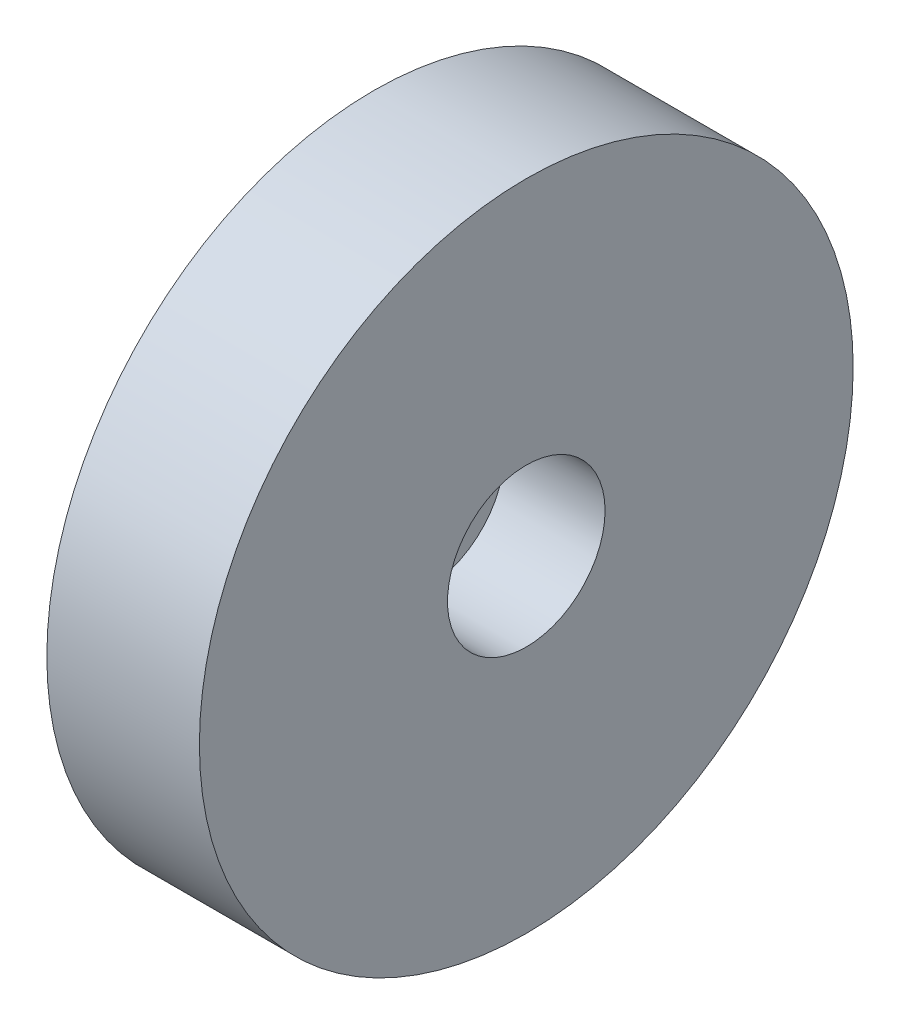
SolidWorks part; units mm, degrees
ref_plane "Plane1" through (0, 0, 0) normal (0, 0, 1) x (1, 0, 0)
ref_plane "Plane2" through (0, 0, 0) normal (0, 1, 0) x (1, 0, 0)
ref_plane "Plane3" through (0, 0, 0) normal (1, 0, 0) x (0, 0, -1)
sketch "HoldingSke" plane through (0, 0, 0) normal (0, 1, 0) x (1, 0, 0)
  line L0 (0, 0) -> (0.9272, -0.3746)
  line L1 (-15, 0) -> (100, 0) construction
  line L2 (0, 0) -> (-2.1039, 2.3779)
  line L3 (0, 0) -> (-11.863, 4.5341)
  line L4 (0, 0) -> (8.0072, 3.2351)
  line L5 (0, 0) -> (-46.8476, -17.4728)
  line L6 (0, 0) -> (-3.7718, -2.5448)
  line L7 (-2.1039, 2.3779) -> (8.6586, 51.2059)
  line L8 (-76.2, 54.61) -> (-75.5, 54.61)
  line L9 (-71.009, 38.7566) -> (-53.1078, 45.2721)
  line L10 (-76.2, 71.12) -> (104.1128, 71.12)
  line L11 (0, 0) -> (-4.55, 0)
  line L12 (-76.2, 101.6) -> (-76.162, 101.6)
  line L13 (24.9733, 27.94) -> (52.9518, 28.4284)
  line L14 (24.9733, 27.94) -> (24.9743, 27.94)
  line L15 (24.9733, 27.94) -> (100.4006, 29.5858)
  line L16 (-63.627, -1) -> (-12.827, -1)
  circle A0 centre (0, 0) radius 2
  circle A1 centre (0, 0) radius 9.749
  circle A2 centre (0, 0) radius 37.5
  circle A3 centre (0, 0) radius 2
  dimension "Num_teeth" = 22
  dimension "Pitch_radius" = 180.3128
  dimension "Width" = 4.55
  dimension "Thickness" = 4.55
sketch "BasProSke" plane through (0, 0, 0) normal (0, 1, 0) x (1, 0, 0)
  line L0 (-10, 0) -> (60, 0) construction
  line L1 (0, 0) -> (0, 12)
  line L2 (0, 0) -> (4.55, 0)
  line L3 (4.55, 0) -> (4.55, 12)
  line L4 (4.55, 12) -> (0, 12)
  dimension "Thickness" = 4.55
  dimension "Diameter" = 24
revolve "Base-Revolve" add sketch "BasProSke" angle 360 about L0
sketch "TooCutSke" plane through (0, 0, 0) normal (1, 0, 0) x (0, 0, -1)
  line L1 (0, 0) -> (0, 107) construction
  line L2 (0, 0) -> (-2.273, 10.7626) construction
  line L3 (0, 0) -> (-3.1242, 21.7296) construction
  line L4 (-2.273, 10.7626) -> (-1.5621, 10.8648) construction
  arc A0 (1.7556, 9.5896) -> (-1.7556, 9.5896) centre (0, 0) ccw
  arc A1 (3.0039, 11.6442) -> (-3.0039, 11.6442) centre (0, 0) ccw
  circle A2 centre (0, 0) radius 11 construction
  circle A3 centre (0, 0) radius 10.3366 construction
  arc A4 (-1.7556, 9.5896) -> (-3.0039, 11.6442) centre (-5.997, 8.4191) ccw
  arc A5 (3.0039, 11.6442) -> (1.7556, 9.5896) centre (5.997, 8.4191) ccw
extrude "ToothCut" cut sketch "TooCutSke" along normal through all
fillet "Breaks" [suppressed] radius 0.02 tangent propagation no
fillet "RootFillets" [suppressed] radius 0.251
pattern_circular "TeethCuts" count 22 every 16.364 about axis through (-10, 0, 0) along (1, 0, 0) of "ToothCut", "RootFillets", "Breaks"
sketch "HubNeaOneSke" plane through (0, 0, 0) normal (-1, 0, 0) x (0, 0, 1)
  circle A0 centre (0, 0) radius 9.749
  dimension "Diameter" = 19.498
extrude "HubNearOne" [suppressed] add sketch "HubNeaOneSke" along normal blind 45.4501
sketch "HubNeaBotSke" plane through (0, 0, 0) normal (-1, 0, 0) x (0, 0, 1)
  circle A0 centre (0, 0) radius 9.749
  dimension "Diameter" = 19.498
extrude "HubNearBoth" [suppressed] add sketch "HubNeaBotSke" along normal blind 22.725
ref_plane "FarPln" through (4.55, 0, 0) normal (1, 0, 0) x (0, 0, -1)
sketch "HubFarSke" plane through (4.55, 0, 0) normal (1, 0, 0) x (0, 0, -1)
  circle A0 centre (0, 0) radius 9.749
  dimension "Diameter" = 19.498
extrude "HubFar" [suppressed] add sketch "HubFarSke" along normal blind 22.725
sketch "BorSke" plane through (0, 0, 0) normal (1, 0, 0) x (0, 0, -1)
  circle A0 centre (0, 0) radius 1.35
  dimension "Diameter" = 2.7
extrude "Bore" cut sketch "BorSke" along normal mid plane 100.0001
sketch "KeySke" plane through (0, 0, 0) normal (1, 0, 0) x (0, 0, -1)
  line L0 (-0.8, 0) -> (-0.8, 2.7)
  line L1 (-0.8, 2.7) -> (0.8, 2.7)
  line L2 (0.8, 2.7) -> (0.8, 0)
  line L3 (0, 0) -> (0, 34) construction
  line L4 (-0.8, 0) -> (0.8, 0)
  dimension "Width" = 1.6
extrude "Keyway" [suppressed] cut sketch "KeySke" along normal mid plane 100.0001
pattern_circular "Keyway2" [suppressed] count 2 every 90 about axis through (-10, 0, 0) along (1, 0, 0) reverse direction yes
sketch "Sketch1" plane through (0, 0, 0) normal (-1, 0, 0) x (0, 0, 1)
  circle A0 centre (0, 0) radius 4
  circle A1 centre (0, 0) radius 6
  circle A2 centre (0, 0) radius 1.35 construction
  circle A3 centre (0, 0) radius 1.35
  dimension "D1" = 8
  dimension "D2" = 12
extrude "Boss-Extrude1" add sketch "Sketch1" along normal blind 4 contours A0 region at (0, 0, -3.8869)
extrude "Boss-Extrude2" add sketch "Sketch1<4>" along normal blind 1 contours A1 A0 region at (0, 0, -5.8303)
sketch "Sketch1<4>" plane through (0, 0, 0) normal (-1, 0, 0) x (0, 0, 1) same geometry as "Sketch1"
sketch "Sketch2" plane through (4.55, 0, 0) normal (1, 0, 0) x (0, 0, -1)
  circle A0 centre (0, 0) radius 2.35
  circle A1 centre (0, 0) radius 4.35
  dimension "D1" = 4.7
  dimension "D2" = 2
extrude "Boss-Extrude3" [suppressed] add sketch "Sketch2" along normal blind 2.5
fillet "Fillet1" [suppressed] radius 0.5
extrude "Cut-Extrude1" cut sketch "Sketch2<2>" against normal blind 3 contours A0 region at (4.55, 0, 0)
sketch "Sketch2<2>" plane through (4.55, 0, 0) normal (1, 0, 0) x (0, 0, -1) same geometry as "Sketch2"
equation "' \"Module@HoldingSke\" = 6.35"
equation "' \"Num_teeth@HoldingSke\" = 12"
equation "' \"Ap@HoldingSke\" =  20"
equation "' \"Ap@HoldingSke\" = 20"
equation "' \"Width@HoldingSke\" = 0.5 * 25.4"
equation "' \"Hub_dia@HoldingSke\"= 1 * 25.4"
equation "' \"Hub_dia@HoldingSke\" = 1 * 25.4"
equation "' \"Overall_len@HoldingSke\" = 1.0 * 25.4"
equation "' \"Bore@HoldingSke\" = 0.75 * 25.4"
equation "' \"T_dim@HoldingSke\" = 0.1 * 25.4"
equation "' \"Width@KeySke\" = 0.25 * 25.4"
equation "' \"Show_teeth@HoldingSke\" = 13"
equation "' \"Backlash@HoldingSke\" = 0.009 * 25.4"
equation "' \"Addendum_fac@HoldingSke\" = 1.0"
equation "' \"Dedendum_fac@HoldingSke\" = 1.25"
equation "' \"Dedendum_add@HoldingSke\" = 0.00005 * 25.4"
equation "' \"Clearance_fac@HoldingSke\" = 0.25"
equation "\"Pitch@HoldingSke\" = 1 / \"Module@HoldingSke\""
equation "\"Overcut_dia@TooCutSke\" = (\"Num_teeth@HoldingSke\" + 2 * \"Addendum_fac@HoldingSke\") / \"Pitch@HoldingSke\" + 0.002 * 25.4"
equation "\"Pitch_dia@TooCutSke\" = \"Num_teeth@HoldingSke\" / \"Pitch@HoldingSke\""
equation "\"Base_dia@TooCutSke\" = \"Num_teeth@HoldingSke\" / \"Pitch@HoldingSke\" * cos((\"Ap@HoldingSke\"  * 3.14159265 / 180))"
equation "\"Root_dia@TooCutSke\" = (\"Num_teeth@HoldingSke\" + 2) / \"Pitch@HoldingSke\" - 2 * (\"Addendum_fac@HoldingSke\" + \"Dedendum_fac@HoldingSke\") / \"Pitch@HoldingSke\" - \"Dedendum_add@HoldingSke\" * 2"
equation "\"Half_ang@TooCutSke\" = 180 / \"Num_teeth@HoldingSke\""
equation "\"Half_CT@TooCutSke\" = \"Num_teeth@HoldingSke\" / \"Pitch@HoldingSke\" * sin((3.14159265 / 2 / \"Num_teeth@HoldingSke\")) / 2 - 7 * \"Backlash@HoldingSke\" / 4"
equation "\"Flank_rad@TooCutSke\" = \"Num_teeth@HoldingSke\" / \"Pitch@HoldingSke\" / 5"
equation "\"Radius@RootFillets\" = \"Clearance_fac@HoldingSke\" / \"Pitch@HoldingSke\" + \"Dedendum_add@HoldingSke\""
equation "\"Break_rad@Breaks\" = 0.02 / \"Pitch@HoldingSke\""
equation "\"Thickness@HoldingSke\" = \"Width@HoldingSke\""
equation "\"OAL@HoldingSke\" = \"Thickness@HoldingSke\""
equation "\"MHD@HoldingSke\" = (\"Num_teeth@HoldingSke\" + 2) / \"Pitch@HoldingSke\" - 2 * (\"Addendum_fac@HoldingSke\" + \"Dedendum_fac@HoldingSke\")  / \"Pitch@HoldingSke\" - \"Dedendum_add@HoldingSke\" * 2"
equation "\"MBD@HoldingSke\" = (\"Num_teeth@HoldingSke\" + 2) / \"Pitch@HoldingSke\" - 2 * (\"Addendum_fac@HoldingSke\" + \"Dedendum_fac@HoldingSke\")  / \"Pitch@HoldingSke\" - \"Dedendum_add@HoldingSke\" * 2 - 0.002 * 25.4"
equation "\"MHD@HoldingSke\" = ((sgn( \"MHD@HoldingSke\" - \"Hub_dia@HoldingSke\" )-1)*( \"MHD@HoldingSke\" - \"Hub_dia@HoldingSke\" ))/-2+ \"Hub_dia@HoldingSke\""
equation "\"MBD@HoldingSke\" = ((sgn( \"MBD@HoldingSke\" - \"Bore@HoldingSke\" )-1)*( \"MBD@HoldingSke\" - \"Bore@HoldingSke\" ))/-2+ \"Bore@HoldingSke\""
equation "\"OAL@HoldingSke\" = ((sgn( \"OAL@HoldingSke\" - \"Overall_len@HoldingSke\" )+1)*( \"OAL@HoldingSke\" - \"Overall_len@HoldingSke\" ))/2 + \"Overall_len@HoldingSke\" + 0.000002 * 25.4"
equation "\"Num_teeth@TeethCuts\" = int( \"Show_teeth@HoldingSke\" ) + 1"
equation "\"Num_teeth@TeethCuts\" = ((sgn( \"Num_teeth@TeethCuts\" - \"Num_teeth@HoldingSke\" )-1)*( \"Num_teeth@TeethCuts\" - \"Num_teeth@HoldingSke\" ))/-2+ \"Num_teeth@HoldingSke\""
equation "\"Num_teeth@TeethCuts\" = ((sgn( \"Num_teeth@TeethCuts\" - 2.0)+1)*( \"Num_teeth@TeethCuts\" - 2.0))/2 +2.0"
equation "\"Angle@TeethCuts\" = 360.0 / \"Num_teeth@HoldingSke\""
equation "\"Diameter@BasProSke\" = (\"Num_teeth@HoldingSke\" + 2 * \"Addendum_fac@HoldingSke\") / \"Pitch@HoldingSke\""
equation "\"Thickness@BasProSke\"  = \"Thickness@HoldingSke\""
equation "' \"Fillet_rad@BasProSke\" =  \"Thickness@HoldingSke\" * 0.05"
equation "' \"Fillet_rad@BasProSke\" = \"Thickness@HoldingSke\" * 0.05"
equation "\"MHD@HoldingSke\" = ((sgn( \"MHD@HoldingSke\" - \"Root_dia@TooCutSke\" )-1)*( \"MHD@HoldingSke\" - \"Root_dia@TooCutSke\" ))/-2+ \"Root_dia@TooCutSke\""
equation "\"Diameter@HubNeaOneSke\" = \"MHD@HoldingSke\""
equation "\"Length@HubNearOne\" = \"OAL@HoldingSke\" - \"Thickness@BasProSke\""
equation "\"Diameter@HubNeaBotSke\" = \"MHD@HoldingSke\""
equation "\"Length@HubNearBoth\" = ( \"OAL@HoldingSke\" - \"Thickness@BasProSke\" ) / 2.0"
equation "\"Thickness@FarPln\" = \"Thickness@BasProSke\""
equation "\"Diameter@HubFarSke\" = \"MHD@HoldingSke\""
equation "\"Length@HubFar\" = ( \"OAL@HoldingSke\" - \"Thickness@BasProSke\" ) / 2.0"
equation "\"Diameter@BorSke\"=2.7"
equation "\"D1@Bore\" = \"OAL@HoldingSke\" * 2.0"
equation "\"D1@Keyway\" = \"OAL@HoldingSke\" * 2.0"
equation "\"Offset@KeySke\" = \"T_dim@HoldingSke\" + \"MBD@HoldingSke\" / 2.0"
